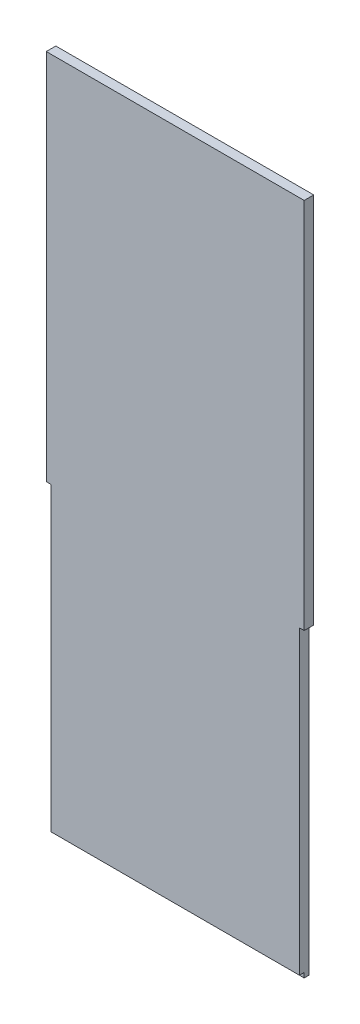
SolidWorks part; units mm, degrees
ref_plane "Front Plane" through (0, 0, 0) normal (0, 0, 1) x (1, 0, 0)
ref_plane "Top Plane" through (0, 0, 0) normal (0, 1, 0) x (1, 0, 0)
ref_plane "Right Plane" through (0, 0, 0) normal (1, 0, 0) x (0, 0, -1)
sketch "Sketch1" plane through (0, 0, 0) normal (0, 0, 1) x (1, 0, 0)
  line L0 (0, 406.4) -> (-6.35, 406.4)
  line L1 (0, 0) -> (330.2, 0)
  line L2 (0, 0) -> (0, 406.4)
  line L4 (330.2, 0) -> (330.2, 406.4)
  line L5 (-6.35, 406.4) -> (-6.35, 901.7)
  line L7 (165.1, 914.4) -> (165.1, 50914.4) construction
  line L9 (330.2, 406.4) -> (336.55, 406.4)
  line L10 (336.55, 406.4) -> (336.55, 901.7)
  line L11 (-6.35, 901.7) -> (336.55, 901.7)
  dimension "D1" = 330.2
  dimension "D2" = 901.7
  dimension "D3" = 6.35
  dimension "D4" = 495.3
extrude "Boss-Extrude1" add sketch "Sketch1" along normal blind 12.7
sketch "Sketch2" plane through (0, 0, 12.7) normal (0, 0, 1) x (1, 0, 0)
  line L0 (0, 406.4) -> (0, 0) construction
  line L1 (0, 6.35) -> (330.2, 6.35)
  line L2 (0, 6.35) -> (0, 0)
  line L3 (0, 0) -> (330.2, 0)
  line L4 (330.2, 6.35) -> (330.2, 0)
  line L5 (330.2, 0) -> (330.2, 406.4) construction
  line L6 (0, 0) -> (330.2, 0) construction
  dimension "D1" = 6.35
extrude "Cut-Extrude1" cut sketch "Sketch2" against normal blind 6.35
